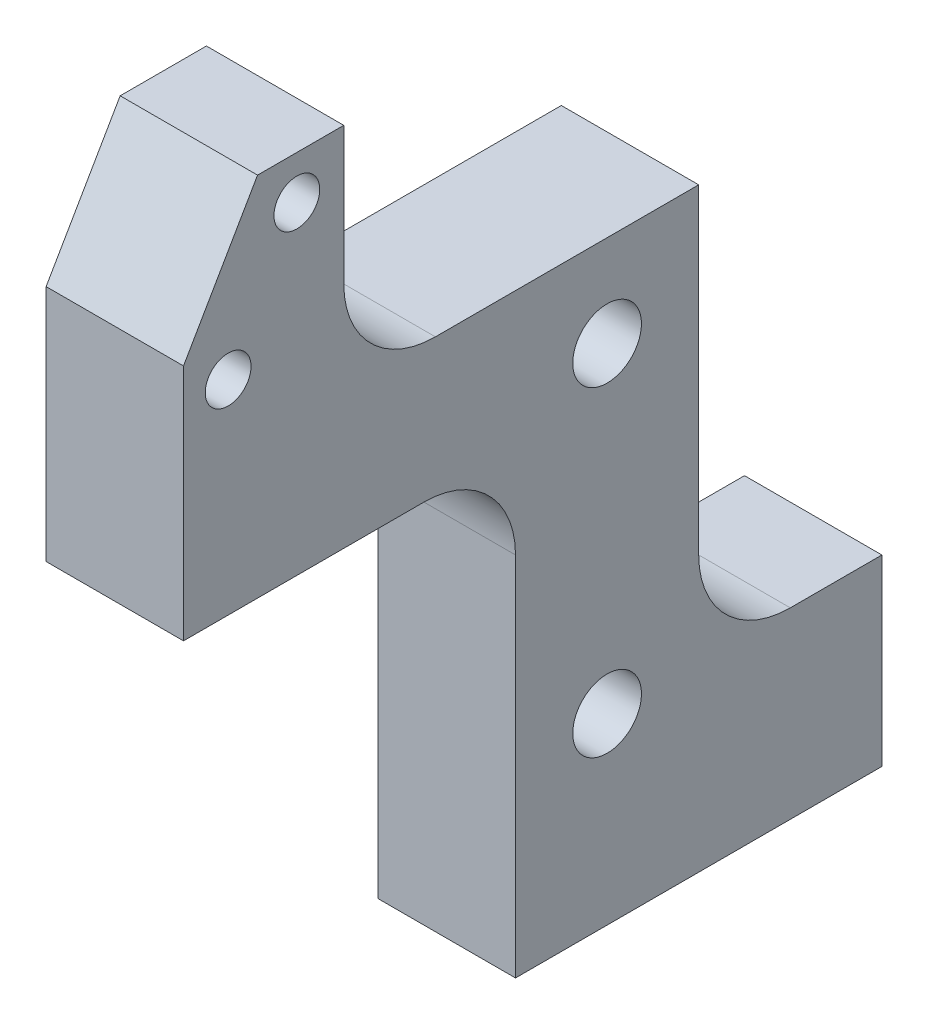
SolidWorks part; units mm, degrees
ref_plane "Front Plane" through (0, 0, 0) normal (0, 0, 1) x (1, 0, 0)
ref_plane "Top Plane" through (0, 0, 0) normal (0, 1, 0) x (1, 0, 0)
ref_plane "Right Plane" through (0, 0, 0) normal (1, 0, 0) x (0, 0, -1)
sketch "Sketch1" plane through (0, 0, 0) normal (1, 0, 0) x (0, 0, -1)
  line L0 (30.5, 0) -> (14.5, 0)
  line L1 (14.5, 0) -> (14.5, 20)
  line L2 (14.5, 20) -> (0, 20)
  line L3 (0, 20) -> (0, 30.4)
  line L4 (0, 30.4) -> (3.2332, 36)
  line L5 (3.2332, 36) -> (7, 36)
  line L6 (7, 36) -> (7, 26)
  line L7 (7, 26) -> (22.5, 26)
  line L8 (22.5, 26) -> (22.5, 8)
  line L9 (22.5, 8) -> (30.5, 8)
  line L10 (30.5, 8) -> (30.5, 0)
  line L11 (1.95, 28.91) -> (4.95, 34.1062) construction
  circle A0 centre (18.5, 8) radius 1.5
  circle A1 centre (18.5, 22) radius 1.5
  circle A2 centre (1.95, 28.91) radius 1
  circle A3 centre (4.95, 34.1062) radius 1
  dimension "D3" = 3
  dimension "D4" = 2
  dimension "D1" = 8
  dimension "D2" = 14.5
  dimension "D5" = 16
  dimension "D6" = 12
  dimension "D7" = 14
  dimension "D8" = 8
  dimension "D9" = 20
  dimension "D10" = 120
  dimension "D11" = 5.6
  dimension "D12" = 6
  dimension "D13" = 1.95
  dimension "D14" = 7.09
  dimension "D15" = 7
  dimension "D16" = 10
  dimension "D17" = 36
extrude "Boss-Extrude1" add sketch "Sketch1" along normal blind 6
fillet "Fillet1" radius 4 3 edges at (3, 8, -22.5) (3, 20, -14.5) (3, 26, -7)
hole_wizard "Tap Drill for M3x0.5 Tap1" positions "Sketch3" profile "Sketch2" hole size "M3x0.5" standard "ANSI Metric"
sketch "Sketch3" plane through (0, 0, 0) normal (0, -1, 0) x (-1, 0, 0)
  line L0 (-6, 14.5) -> (-6, 30.5) construction
  line L1 (-6, 30.5) -> (0, 30.5) construction
  point P0 (-3, 17.5)
  point P2 (-3, 27.5)
  dimension "D1" = 3
  dimension "D2" = 3
  dimension "D3" = 10
sketch "Sketch2" plane through (3, 0, -17.5) normal (1, 0, 0) x (0, 0, -1)
  line L0 (0, 0) -> (0, 4)
  line L1 (0, 4) -> (1.25, 4)
  line L2 (1.25, 4) -> (1.25, 0)
  line L5 (1.25, 0) -> (0, 0)
  line L10 (0, 4) -> (-1.25, 4) construction
  line L11 (0, -6.35) -> (0, 107.95) construction
  dimension "Hole Dia." = 2.5
  dimension "Hole Depth" = 4
  dimension "Drill Angle" = 180
sketch "Sketch4" plane through (0, 0, 0) normal (0, -1, 0) x (1, 0, 0)
  line L0 (6, -30.5) -> (0, -30.5) construction
  line L1 (0, -14.5) -> (0, -30.5) construction
  circle A0 centre (3, -22.5) radius 1
  dimension "D1" = 2
  dimension "D2" = 8
  dimension "D3" = 3
extrude "Cut-Extrude1" cut sketch "Sketch4" against normal blind 3
sketch "Sketch5" plane through (0, 0, 0) normal (1, 0, 0) x (0, 0, -1)
  circle A0 centre (18.5, 22) radius 3
  circle A1 centre (18.5, 8) radius 3
  dimension "D1" = 6
extrude "Cut-Extrude2" cut sketch "Sketch5" along normal blind 3
